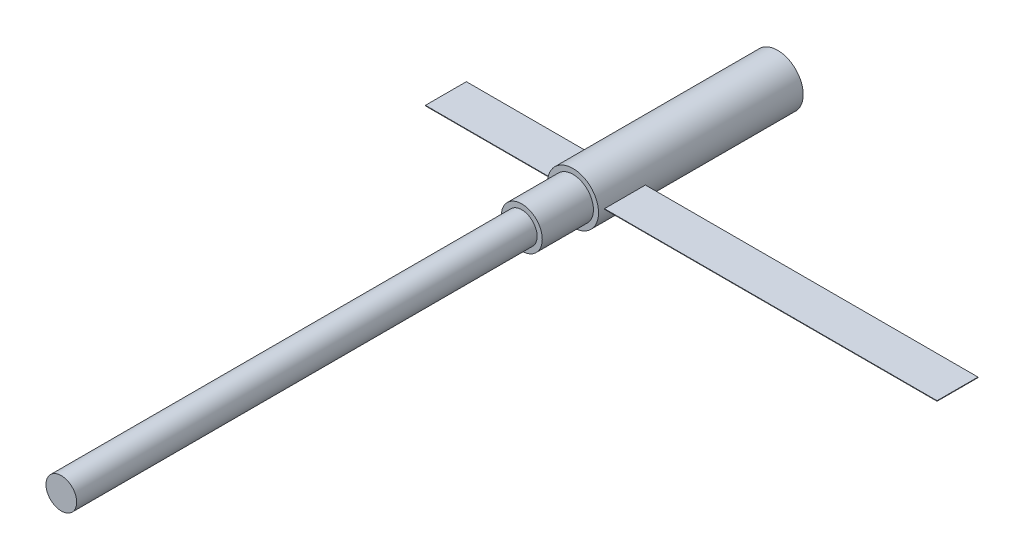
SolidWorks part; units mm, degrees
ref_plane "前视基准面" through (0, 0, 0) normal (0, 0, 1) x (1, 0, 0)
ref_plane "上视基准面" through (0, 0, 0) normal (0, 1, 0) x (1, 0, 0)
ref_plane "右视基准面" through (0, 0, 0) normal (1, 0, 0) x (0, 0, -1)
other "Configuration Table"
sketch "草图1" plane through (0, 0, 0) normal (0, 0, 1) x (1, 0, 0)
  circle A0 centre (0, 0) radius 500
extrude "凸台-拉伸1" add sketch "草图1" along normal blind 4000
sketch "草图2" plane through (0, 0, 4000) normal (0, 0, 1) x (1, 0, 0)
  circle A0 centre (0, 0) radius 300
  dimension "D1" = 600
extrude "凸台-拉伸2" add sketch "草图2" along normal blind 10000
sketch "草图6" plane through (0, 0, 0) normal (0, 1, 0) x (1, 0, 0)
  line L0 (7000, -500) -> (7000, -1300)
  line L2 (7000, -500) -> (-3000, -500)
  line L3 (-3000, -500) -> (-3000, -1300)
  line L4 (7000, -1300) -> (-3000, -1300)
  dimension "D1" = 10000
extrude "凸台-拉伸6" add sketch "草图6" along normal blind 10 separate body contours L4 L3 L2 L0
move or copy body "实体-移动/复制1" bodies to move or copy 111 copy no translate (0, 0, 1049.3595) parameters "D1"=0, "D2"=0, "D3"=1049.3595
move or copy body "实体-移动/复制2" bodies to move or copy 112 copy no translate (0, 0, 2037.4174) parameters "D1"=0, "D2"=0, "D3"=2037.4174
move or copy body "实体-移动/复制3" bodies to move or copy 113 copy no translate (0, 0, -503.2988) parameters "D1"=0, "D2"=0, "D3"=503.2988
sketch "草图7" plane through (0, 0, 4000) normal (0, 0, 1) x (1, 0, 0)
  circle A0 centre (0, 0) radius 400
extrude "凸台-拉伸7" add sketch "草图7" along normal blind 1000
ref_plane "基准面1" through (0, 0, 5800) normal (0, 0, 1) x (1, 0, 0)
ref_point "点2"
sketch "草图8" plane through (0, 0, 14000) normal (0, 0, 1) x (1, 0, 0)
  line L0 (0, 0) -> (0, 300)
  circle A0 centre (0, 0) radius 300 construction
ref_plane "基准面2" through (0, 0, 0) normal (1, 0, 0) x (0, 1, 0)
ref_plane "基准面4" through (0, 295, 0) normal (0, -1, 0) x (-1, 0, 0)
ref_axis "基准轴1" through (435.3819, 295, 5800) along (-1, 0, 0)
ref_axis "基准轴2" through (0, 449.0274, 5800) along (0, -1, 0)
